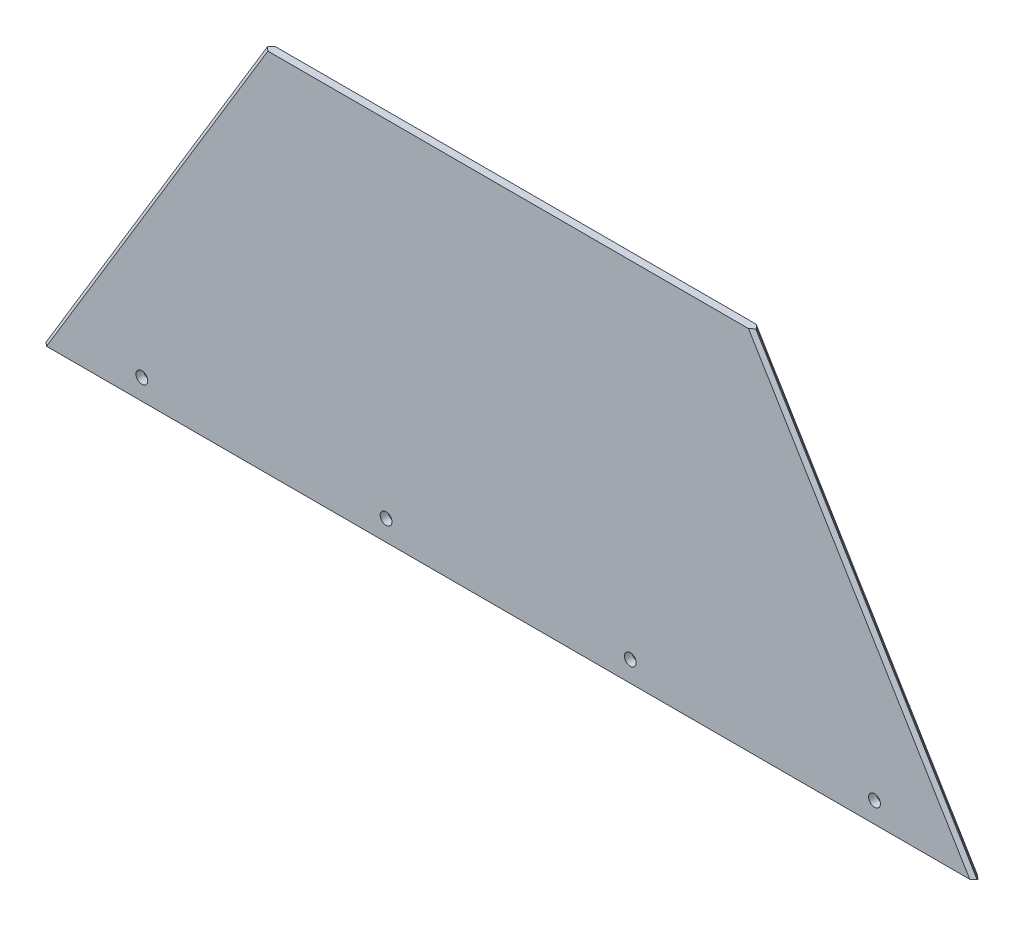
SolidWorks part; units mm, degrees
material "Printed Circuit Board"
ref_plane "Front Plane" through (0, 0, 0) normal (0, 0, 1) x (1, 0, 0)
ref_plane "Top Plane" through (0, 0, 0) normal (0, 1, 0) x (1, 0, 0)
ref_plane "Right Plane" through (0, 0, 0) normal (1, 0, 0) x (0, 0, -1)
sketch "Sketch1" plane through (0, 0, 0) normal (0, 0, 1) x (1, 0, 0)
  line L0 (0, 0) -> (193.675, 0)
  line L1 (193.675, 0) -> (101.6, 152.4)
  line L2 (101.6, 152.4) -> (0, 152.4)
  line L3 (0, 152.4) -> (-101.6, 152.4)
  line L4 (-101.6, 152.4) -> (-193.675, 0)
  line L5 (-193.675, 0) -> (0, 0)
  line L6 (0, 0) -> (0, 152.4) construction
  dimension "D1" = 152.4
  dimension "D2" = 387.35
  dimension "D3" = 203.2
extrude "Extrude1" add sketch "Sketch1" along normal mid plane 3.175
ref_plane "Plane1" through (0, 0, 0) normal (-1, 0, 0) x (0, 0, 1)
chamfer "Chamfer1" distance 1.397 angle 45 4 edges at (147.6375, 76.2, -1.5875) (-147.6375, 76.2, -1.5875) (147.6375, 76.2, 1.5875) (-147.6375, 76.2, 1.5875)
sketch "Sketch2" plane through (0, 0, 1.5875) normal (0, 0, 1) x (1, 0, 0)
  line L0 (193.675, 0) -> (50.8, 0) construction
  line L1 (-192.0428, 0) -> (192.0428, 0) construction
  line L2 (50.8, 0) -> (50.8, 8.5852) construction
  line L3 (0, 1.7463) -> (0, -1.7463) construction
  dimension "D1" = 50.8
  dimension "D2" = 8.5852
hole_wizard "#10 (0.1935) Diameter Hole1" positions "3DSketch1" profile "Sketch4" hole size "#10" standard "Ansi Inch" end condition through all
sketch3d "3DSketch1"
  point P0 (50.8, 8.5852, 1.5875)
sketch "Sketch4" plane through (50.8, 8.5852, 1.5875) normal (1, 0, 0) x (0, -1, 0)
  line L0 (0, 0) -> (0, 3.175)
  line L1 (0, 3.175) -> (2.4574, 3.175)
  line L2 (2.4574, 3.175) -> (2.4574, 0)
  line L5 (2.4574, 0) -> (0, 0)
  line L11 (0, -6.35) -> (0, 107.95) construction
  dimension "Thru Hole Dia." = 4.9149
  dimension "Thru Hole Depth" = 3.175
pattern_linear "LPattern2" count 3 spacing 101.6 along (-1, 0, 0) count 2 spacing 101.6 along (1, 0, 0) of "#10 (0.1935) Diameter Hole1"
